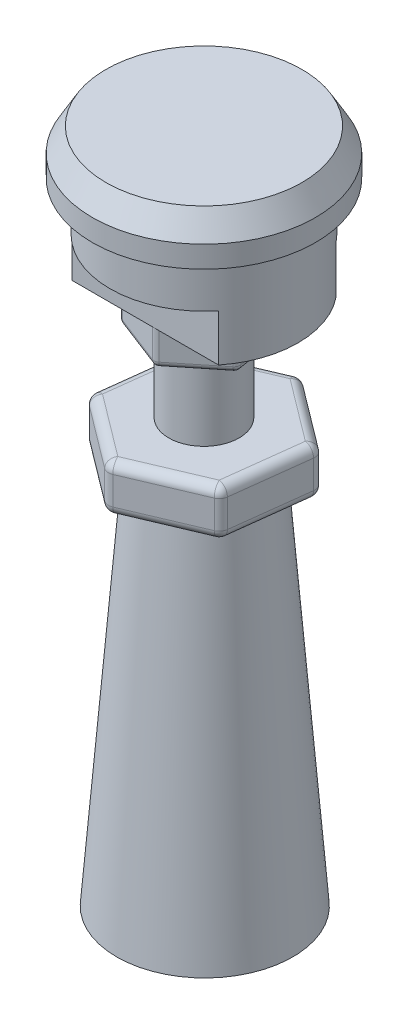
SolidWorks part; units mm, degrees
material "合金鋼 (SS)"
ref_plane "正面" through (0, 0, 0) normal (0, 0, 1) x (1, 0, 0)
ref_plane "平面" through (0, 0, 0) normal (0, 1, 0) x (1, 0, 0)
ref_plane "右側面" through (0, 0, 0) normal (1, 0, 0) x (0, 0, -1)
sketch "ｽｹｯﾁ1" plane through (0, 0, 0) normal (0, 1, 0) x (1, 0, 0)
  circle A0 centre (0, 0) radius 8
extrude "ﾎﾞｽ - 押し出し2" add sketch "ｽｹｯﾁ1" along normal blind 7
sketch "ｽｹｯﾁ3" plane through (0, 0, 0) normal (0, -1, 0) x (1, 0, 0)
  line L1 (6.245, 5) -> (-6.245, 5)
  line L2 (-6.245, -5) -> (6.245, -5)
  circle A0 centre (0, 0) radius 8 construction
  arc A1 (-6.245, 5) -> (6.245, 5) centre (0, 0) cw
  arc A2 (-6.245, -5) -> (6.245, -5) centre (0, 0) ccw
  point P9 (0, 5)
  point P13 (0, 0)
  dimension "D1" = 2
extrude "ｶｯﾄ - 押し出し1" cut sketch "ｽｹｯﾁ3" against normal blind 4
sketch "ｽｹｯﾁ4" plane through (0, 0, 0) normal (0, -1, 0) x (1, 0, 0)
  line L1 (-0.7783, -5) -> (3.941, -3.174)
  line L2 (3.941, -3.174) -> (4.7193, 1.826)
  line L3 (4.7193, 1.826) -> (0.7783, 5)
  line L4 (0.7783, 5) -> (-3.941, 3.174)
  line L5 (-3.941, 3.174) -> (-4.7193, -1.826)
  line L6 (-4.7193, -1.826) -> (-0.7783, -5)
  circle A0 centre (0, 0) radius 4.3823 construction
extrude "ﾎﾞｽ - 押し出し3" add sketch "ｽｹｯﾁ4" along normal blind 3
sketch "ｽｹｯﾁ5" plane through (0, -3, 0) normal (0, -1, 0) x (1, 0, 0)
  circle A0 centre (0, 0) radius 3
extrude "ﾎﾞｽ - 押し出し4" add sketch "ｽｹｯﾁ5" along normal blind 6.5
sketch "ｽｹｯﾁ6" plane through (0, -9.5, 0) normal (0, -1, 0) x (1, 0, 0)
  line L1 (-5.997, -4.5132) -> (0.91, -7.4502)
  line L2 (0.91, -7.4502) -> (6.907, -2.937)
  line L3 (6.907, -2.937) -> (5.997, 4.5132)
  line L4 (5.997, 4.5132) -> (-0.91, 7.4502)
  line L5 (-0.91, 7.4502) -> (-6.907, 2.937)
  line L6 (-6.907, 2.937) -> (-5.997, -4.5132)
  circle A0 centre (0, 0) radius 6.5 construction
extrude "ﾎﾞｽ - 押し出し5" add sketch "ｽｹｯﾁ6" along normal blind 4
fillet "ﾌｨﾚｯﾄ1" radius 0.5 12 edges at (0.7783, -1.5, 5) (-3.941, -1.5, 3.174) (-4.7193, -1.5, -1.826) (-0.7783, -1.5, -5) (3.941, -1.5, -3.174) (4.7193, -1.5, 1.826) (2.7488, -3, 3.413) (4.3301, -3, -0.674) (1.5814, -3, -4.087) (-2.7488, -3, -3.413) (-4.3301, -3, 0.674) (-1.5814, -3, 4.087)
fillet "ﾌｨﾚｯﾄ2" radius 0.8 18 edges at (2.5435, -13.5, 5.9817) (-2.5435, -13.5, -5.9817) (3.9085, -13.5, -5.1936) (6.452, -13.5, 0.7881) (-3.9085, -13.5, 5.1936) (-6.452, -13.5, -0.7881) (-6.907, -11.5, 2.937) (2.5435, -9.5, 5.9817) (-0.91, -11.5, 7.4502) (5.997, -11.5, 4.5132) (6.452, -9.5, 0.7881) (6.907, -11.5, -2.937) (0.91, -11.5, -7.4502) (3.9085, -9.5, -5.1936) (-3.9085, -9.5, 5.1936) (-6.452, -9.5, -0.7881) (-2.5435, -9.5, -5.9817) (-5.997, -11.5, -4.5132)
sketch "ｽｹｯﾁ7" plane through (0, -13.5, 0) normal (0, -1, 0) x (1, 0, 0)
  point P0 (0, 0)
sketch "ｽｹｯﾁ8" plane through (0, -13.5, 0) normal (0, -1, 0) x (-1, 0, 0)
  line L0 (-5.259, -3.9577) -> (5.153, 4.0028)
  line L1 (5.259, 3.9577) -> (-0.798, 6.5332) construction
ref_plane "平面2" through (0.0304, 0, -0.0398) normal (-0.6074, 0, 0.7944) x (-0.7944, 0, -0.6074)
sketch "ｽｹｯﾁ9" plane through (0.0304, 0, -0.0398) normal (-0.6074, 0, 0.7944) x (-0.7944, 0, -0.6074)
  line L0 (0, 13.5173) -> (-5, 13.5173)
  line L1 (0, 13.5173) -> (0, 45.5173)
  line L2 (0, 45.5173) -> (-7.5, 45.5173)
  line L3 (-7.5, 45.5173) -> (-5, 13.5173)
revolve "回転2" add sketch "ｽｹｯﾁ9" angle 360 about L1
sketch "ｽｹｯﾁ10" plane through (0, 7, 0) normal (0, 1, 0) x (1, 0, 0)
  circle A0 centre (0, 0) radius 9.5
extrude "ﾎﾞｽ - 押し出し6" add sketch "ｽｹｯﾁ10" along normal blind 5
chamfer "面取り1" distance 2 angle 30 1 edges at (0, 12, 9.5) first distance on face at (0, 12, 9.5)
chamfer "面取り2" distance 2 angle 30 1 edges at (0, 7, 9.5) first distance on face at (0, 7, 8)
